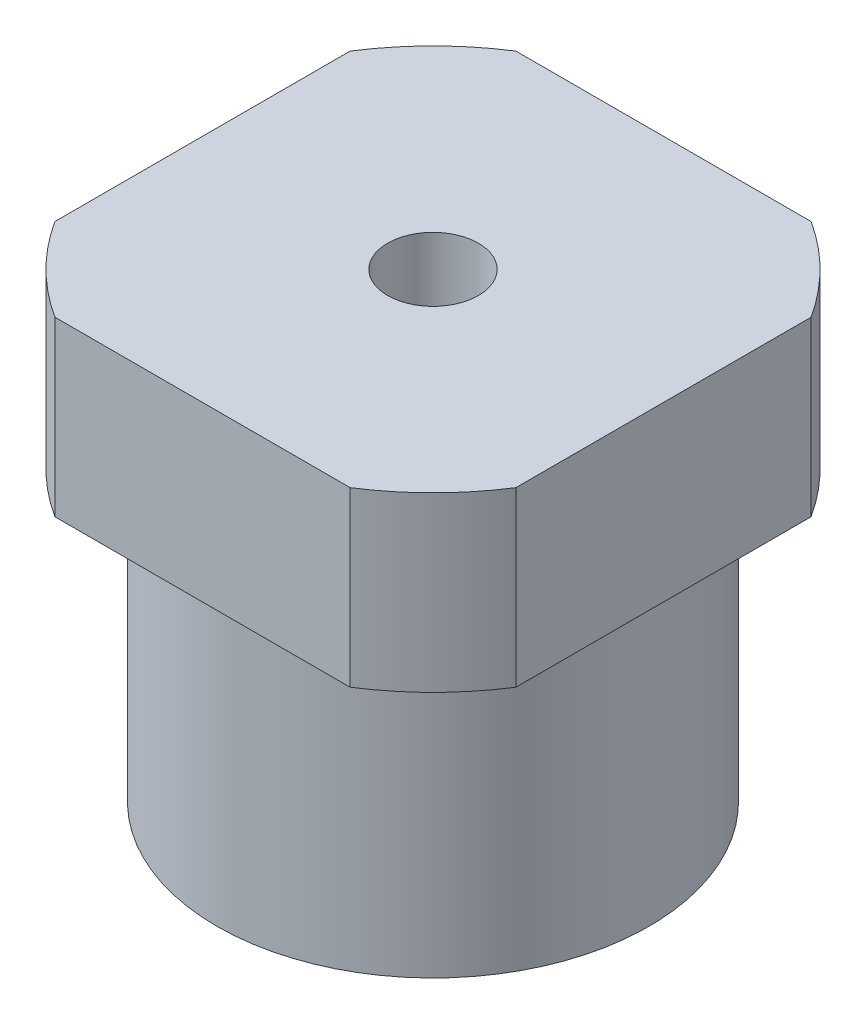
SolidWorks part; units mm, degrees
material "ABS"
ref_plane "Front" through (0, 0, 0) normal (0, 0, 1) x (1, 0, 0)
ref_plane "Top" through (0, 0, 0) normal (0, 1, 0) x (1, 0, 0)
ref_plane "Right" through (0, 0, 0) normal (1, 0, 0) x (0, 0, -1)
ref_axis "Axis1" through (0, 0, 50) along (0, 0, -1)
sketch "Sketch1" plane through (0, 0, 0) normal (0, 1, 0) x (1, 0, 0)
  circle A0 centre (0, 0) radius 9.525
  dimension "D1" = 19.05
extrude "Boss-Extrude1" add sketch "Sketch1" along normal blind 12.7
sketch "Sketch2" plane through (0, 12.7, 0) normal (0, 1, 0) x (1, 0, 0)
  line L1 (-10.16, 10.16) -> (10.16, 10.16)
  line L2 (-10.16, 10.16) -> (-10.16, -10.16)
  line L3 (-10.16, -10.16) -> (10.16, -10.16)
  line L4 (10.16, 10.16) -> (10.16, -10.16)
  line L5 (-10.16, 10.16) -> (10.16, -10.16) construction
  line L6 (-10.16, -10.16) -> (10.16, 10.16) construction
  point P0 (0, 0)
  dimension "D1" = 20.32
  dimension "D2" = 20.32
extrude "Boss-Extrude2" add sketch "Sketch2" along normal blind 7.62
sketch "Sketch3" plane through (0, 20.32, 0) normal (0, 1, 0) x (1, 0, 0)
  line L1 (-10.16, 10.16) -> (10.16, 10.16)
  line L2 (-10.16, 10.16) -> (-10.16, -10.16)
  line L3 (-10.16, -10.16) -> (10.16, -10.16)
  line L4 (10.16, 10.16) -> (10.16, -10.16)
  line L5 (-10.16, 10.16) -> (10.16, -10.16) construction
  line L6 (-10.16, -10.16) -> (10.16, 10.16) construction
  circle A0 centre (0, 0) radius 12.065
  line M1 (10.16, -10.16) -> (10.16, 10.16)
  line M2 (10.16, 10.16) -> (-10.16, 10.16)
  line M3 (-10.16, 10.16) -> (-10.16, -10.16)
  line M4 (-10.16, -10.16) -> (10.16, -10.16)
  dimension "D1" = 24.13
extrude "Cut-Extrude2" cut sketch "Sketch3" against normal through all contours A0 M2 M3 | A0 M1 M2 | A0 M4 M1 | A0 M3 M4 region at (-9.0319, 20.32, -9.0319) region at (9.0319, 20.32, -9.0319) region at (-9.0319, 20.32, 9.0319) region at (9.0319, 20.32, 9.0319)
sketch "Sketch5" plane through (0, 20.32, 0) normal (0, 1, 0) x (1, 0, 0)
  circle A0 centre (0, 0) radius 2
  dimension "D1" = 4
extrude "Cut-Extrude3" cut sketch "Sketch5" against normal through all
